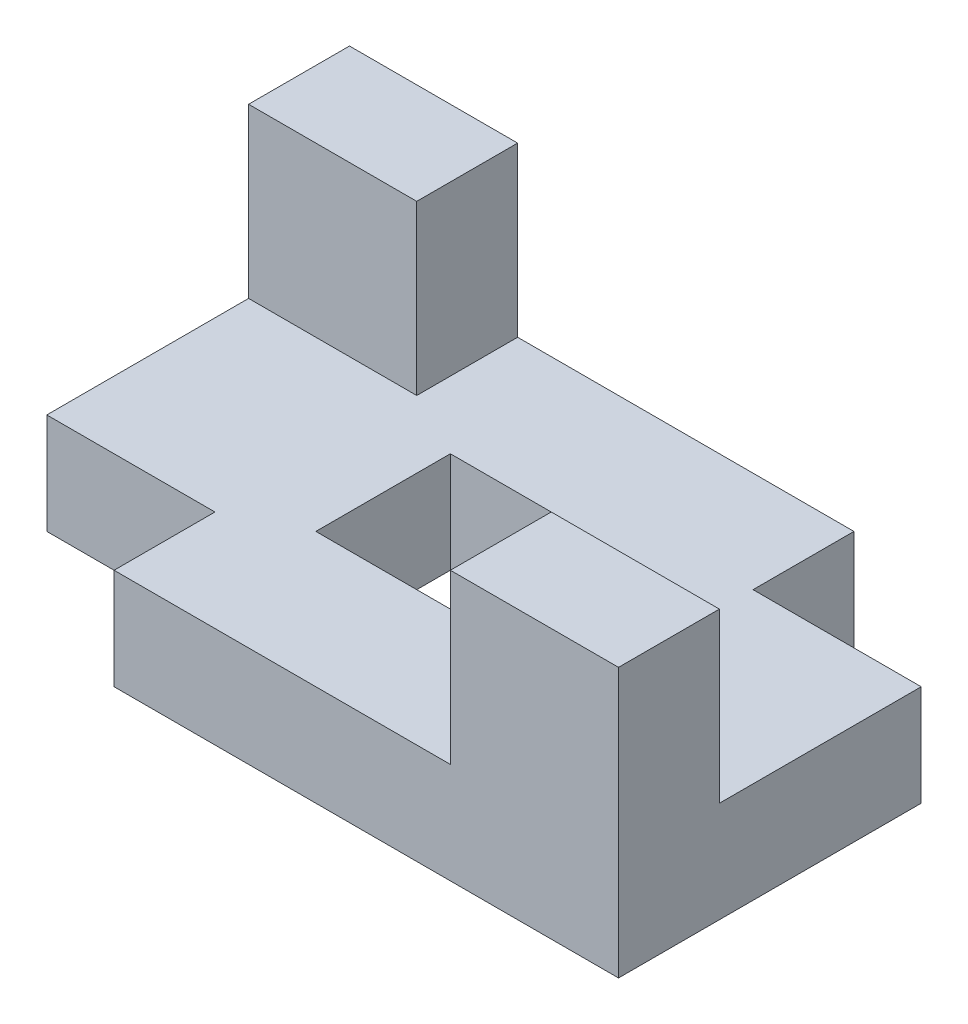
SolidWorks part; units mm, degrees
ref_plane "Front Plane" through (0, 0, 0) normal (0, 0, 1) x (1, 0, 0)
ref_plane "Top Plane" through (0, 0, 0) normal (0, 1, 0) x (1, 0, 0)
ref_plane "Right Plane" through (0, 0, 0) normal (1, 0, 0) x (0, 0, -1)
sketch "Sketch1" plane through (0, 0, 0) normal (0, 1, 0) x (1, 0, 0)
  line L1 (-50, 30) -> (50, 30)
  line L2 (-50, 30) -> (-50, -30)
  line L3 (-50, -30) -> (50, -30)
  line L4 (50, 30) -> (50, -30)
  dimension "D1" = 100
  dimension "D2" = 60
  dimension "D3" = 30
  dimension "D4" = 50
extrude "Boss-Extrude1" add sketch "Sketch1" along normal blind 15 contours L1 L4 L3 L2
sketch "Sketch2" plane through (0, 15, 0) normal (0, 1, 0) x (1, 0, 0)
  line L1 (-50, 30) -> (-25, 30)
  line L2 (-50, 30) -> (-50, 15)
  line L3 (-50, 15) -> (-25, 15)
  line L4 (-25, 30) -> (-25, 15)
  line L5 (50, -30) -> (25, -30)
  line L6 (50, -30) -> (50, -15)
  line L7 (50, -15) -> (25, -15)
  line L8 (25, -30) -> (25, -15)
  dimension "D1" = 25
  dimension "D2" = 15
extrude "Boss-Extrude3" add sketch "Sketch2" along normal blind 25 contours L3 L4 L1 L2
extrude "Boss-Extrude4" add sketch "Sketch2<4>" along normal blind 25
sketch "Sketch2<4>" plane through (0, 15, 0) normal (0, 1, 0) x (1, 0, 0) same geometry as "Sketch2"
sketch "Sketch9" plane through (0, 15, 0) normal (0, 1, 0) x (1, 0, 0)
  line L0 (-50, 15) -> (-25, 15) construction
  line L1 (-25, -15) -> (-50, -15)
  line L2 (-25, -15) -> (-25, -30)
  line L3 (-25, -30) -> (-50, -30)
  line L4 (-50, -15) -> (-50, -30)
  line L5 (50, 30) -> (25, 30)
  line L6 (50, 30) -> (50, 15)
  line L7 (50, 15) -> (25, 15)
  line L8 (25, 30) -> (25, 15)
  line L9 (-25, 30) -> (-25, 15) construction
  line L10 (50, -15) -> (25, -15) construction
  line L11 (25, -15) -> (25, -30) construction
extrude "Cut-Extrude1" cut sketch "Sketch9" against normal blind 100 contours L1 L4 L3 L2
extrude "Cut-Extrude2" cut sketch "Sketch9<3>" against normal blind 100
sketch "Sketch9<3>" plane through (0, 15, 0) normal (0, 1, 0) x (1, 0, 0) same geometry as "Sketch9"
sketch "Sketch11" plane through (0, 15, 0) normal (0, 1, 0) x (1, 0, 0)
  line L0 (-50, 15) -> (-50, -15) construction
  line L1 (-15, -10) -> (15, -10)
  line L2 (-15, -10) -> (-15, 10)
  line L3 (-15, 10) -> (15, 10)
  line L4 (15, -10) -> (15, 10)
  line L5 (-25, 30) -> (25, 30) construction
  point P0 (0, 0)
  dimension "D1" = 30
  dimension "D2" = 20
  dimension "D3" = 35
  dimension "D4" = 20
extrude "Cut-Extrude3" cut sketch "Sketch11" against normal blind 100
